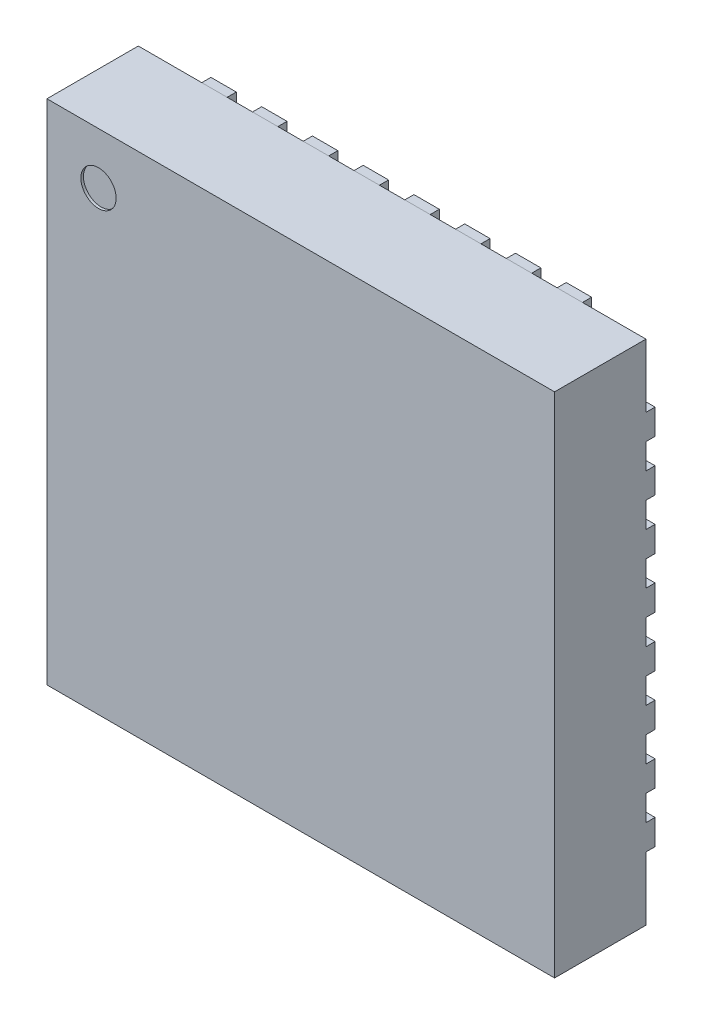
SolidWorks part; units mm, degrees
ref_plane "Front Plane" through (0, 0, 0) normal (0, 0, 1) x (1, 0, 0)
ref_plane "Top Plane" through (0, 0, 0) normal (0, 1, 0) x (1, 0, 0)
ref_plane "Right Plane" through (0, 0, 0) normal (1, 0, 0) x (0, 0, -1)
sketch "Sketch1" plane through (0, 0, 0) normal (0, 0, 1) x (1, 0, 0)
  line L1 (0, 0) -> (5, 0)
  line L2 (0, 0) -> (0, 5)
  line L3 (0, 5) -> (5, 5)
  line L4 (5, 0) -> (5, 5)
  dimension "D1" = 5
  dimension "D2" = 5
extrude "Boss-Extrude1" add sketch "Sketch1" along normal blind 0.9
sketch "Sketch2" plane through (0, 0, 0) normal (0, 0, -1) x (-1, 0, 0)
  line L0 (-2.5, 5) -> (-2.5, 0) construction
  line L1 (-5, 5) -> (0, 5) construction
  line L2 (0, 0) -> (-5, 0) construction
  line L15 (-0.875, 5) -> (-0.625, 5)
  line L16 (-0.625, 5) -> (-0.625, 4.725)
  line L17 (-0.875, 5) -> (-0.875, 4.725)
  line L27 (-1.375, 5) -> (-1.125, 5)
  line L28 (-1.125, 5) -> (-1.125, 4.725)
  line L29 (-1.375, 5) -> (-1.375, 4.725)
  line L39 (-1.875, 5) -> (-1.625, 5)
  line L40 (-1.625, 5) -> (-1.625, 4.725)
  line L41 (-1.875, 5) -> (-1.875, 4.725)
  line L48 (-2.875, 5) -> (-2.625, 5)
  line L49 (-2.625, 5) -> (-2.625, 4.725)
  line L50 (-2.875, 5) -> (-2.875, 4.725)
  line L51 (-2.375, 5) -> (-2.125, 5)
  line L52 (-2.125, 5) -> (-2.125, 4.725)
  line L53 (-2.375, 5) -> (-2.375, 4.725)
  line L54 (-3.375, 5) -> (-3.125, 5)
  line L55 (-3.125, 5) -> (-3.125, 4.725)
  line L56 (-3.375, 5) -> (-3.375, 4.725)
  line L57 (-3.875, 5) -> (-3.625, 5)
  line L58 (-3.625, 5) -> (-3.625, 4.725)
  line L59 (-3.875, 5) -> (-3.875, 4.725)
  line L60 (-4.375, 5) -> (-4.125, 5)
  line L61 (-4.125, 5) -> (-4.125, 4.725)
  line L62 (-4.375, 5) -> (-4.375, 4.725)
  arc A4 (-0.875, 4.725) -> (-0.625, 4.725) centre (-0.75, 4.725) ccw
  arc A8 (-1.375, 4.725) -> (-1.125, 4.725) centre (-1.25, 4.725) ccw
  arc A12 (-1.875, 4.725) -> (-1.625, 4.725) centre (-1.75, 4.725) ccw
  arc A15 (-2.875, 4.725) -> (-2.625, 4.725) centre (-2.75, 4.725) ccw
  arc A16 (-2.375, 4.725) -> (-2.125, 4.725) centre (-2.25, 4.725) ccw
  arc A17 (-3.375, 4.725) -> (-3.125, 4.725) centre (-3.25, 4.725) ccw
  arc A18 (-3.875, 4.725) -> (-3.625, 4.725) centre (-3.75, 4.725) ccw
  arc A19 (-4.375, 4.725) -> (-4.125, 4.725) centre (-4.25, 4.725) ccw
  dimension "D3" = 0.5
extrude "Boss-Extrude3" add sketch "Sketch2" along normal blind 0.09 separate body
ref_plane "Plane1" through (0, 0, 0) normal (0.7071, -0.7071, 0) x (-0.7071, -0.7071, 0)
ref_plane "Plane2" through (2.5, 2.5, 0) normal (-0.7071, -0.7071, 0) x (-0.7071, 0.7071, 0)
ref_axis "Axis1" through (2.5, 2.5, 0.945) along (0, 0, -1)
pattern_circular "CirPattern1" count 4 over 360 about axis through (2.5, 2.5, 0.945) along (0, 0, -1) of "Boss-Extrude3"
sketch "Sketch4" plane through (0, 0, 0.9) normal (0, 0, 1) x (1, 0, 0)
  line L0 (5, 5) -> (0, 5) construction
  line L1 (0, 5) -> (0, 0) construction
  circle A0 centre (0.508, 4.492) radius 0.1737
  dimension "D1" = 0.508
  dimension "D2" = 0.508
extrude "Cut-Extrude1" cut sketch "Sketch4" against normal blind 0.0254
sketch "Sketch5" plane through (0, 0, 0) normal (0, 0, -1) x (-1, 0, 0)
  line L0 (-2.5, 5) -> (-2.5, 0) construction
  line L3 (-1.306, 4.075) -> (-0.925, 4.075) construction
  line L5 (-5, 2.5) -> (0, 2.5) construction
  line L7 (-4.075, 4.075) -> (-1.306, 4.075)
  line L8 (-4.075, 4.075) -> (-4.075, 0.925)
  line L9 (-4.075, 0.925) -> (-0.925, 0.925)
  line L10 (-0.925, 3.694) -> (-0.925, 0.925)
  line L11 (-0.925, 4.075) -> (-0.925, 3.694) construction
  line L14 (-5, 5) -> (0, 5) construction
  line L15 (0, 2.625) -> (0, 2.375) construction
  arc A0 (-1.306, 4.075) -> (-0.925, 3.694) centre (-0.925, 4.075) ccw
  point P4 (-2.5, 5)
  point P9 (0, 2.5)
  point P11 (-2.5, 2.5)
  point P12 (-2.5, 2.5)
  point P17 (-4.075, 2.5)
  point P18 (-2.5, 0.925)
  dimension "D3" = 0.381
  dimension "D1" = 3.15
  dimension "D2" = 3.15
extrude "Boss-Extrude5" add sketch "Sketch5" along normal up to surface (0.09 mm away) up to face at (4.8313, 3.25, -0.09)
